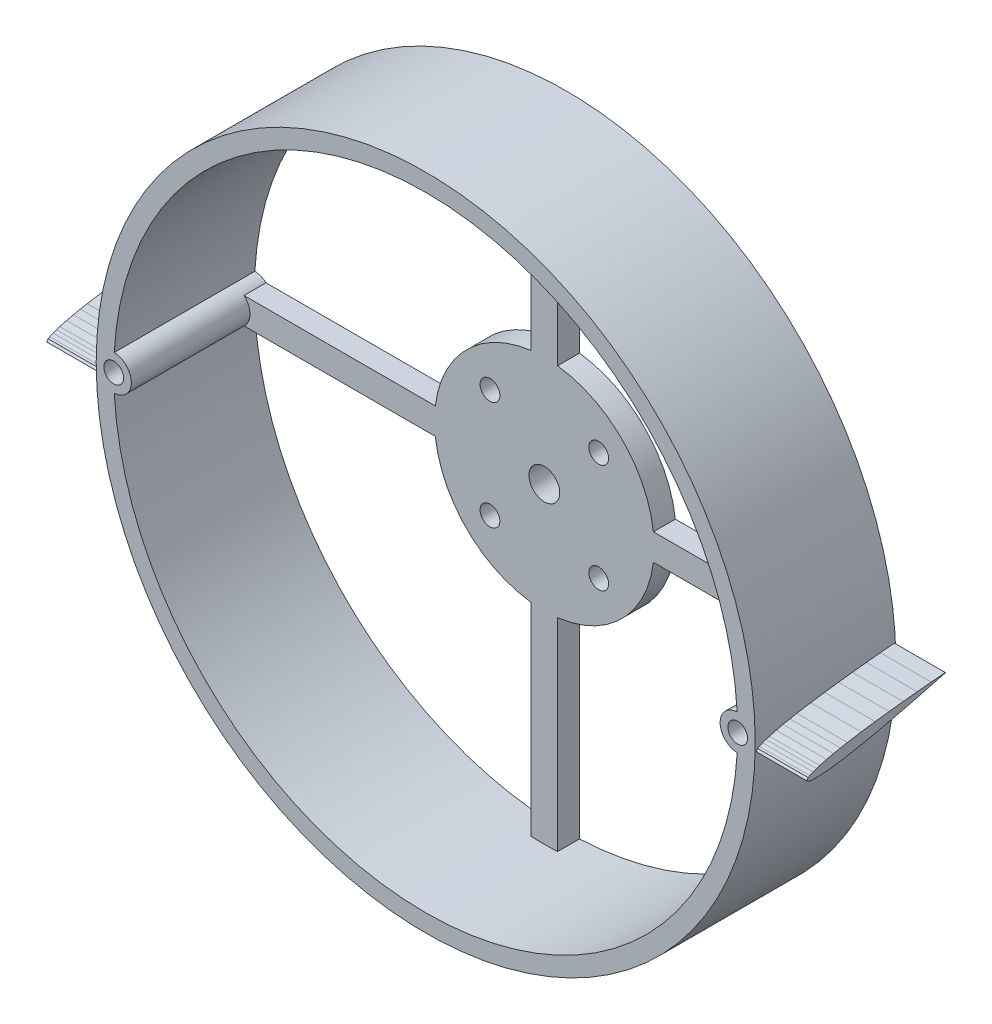
SolidWorks part; units mm, degrees
ref_plane "Front Plane" through (0, 0, 0) normal (0, 0, 1) x (1, 0, 0)
ref_plane "Top Plane" through (0, 0, 0) normal (0, 1, 0) x (1, 0, 0)
ref_plane "Right Plane" through (0, 0, 0) normal (1, 0, 0) x (0, 0, -1)
sketch "Sketch1" plane through (0, 0, 0) normal (0, 0, 1) x (1, 0, 0)
  circle A0 centre (0, 0) radius 75
  dimension "D1" = 150
extrude "Boss-Extrude1" add sketch "Sketch1" along normal blind 5
sketch "Sketch2" plane through (0, 0, 5) normal (0, 0, 1) x (1, 0, 0)
  circle A0 centre (0, 0) radius 3.5
  dimension "D1" = 7
extrude "Cut-Extrude1" cut sketch "Sketch2" against normal through all
sketch "Sketch7" plane through (0, 0, 5) normal (0, 0, 1) x (1, 0, 0)
  line L0 (-707.1068, -707.1068) -> (34648.2323, 34648.2323) construction
  line L1 (-1000, 0) -> (49000, 0) construction
  circle A0 centre (0, 0) radius 17.5 construction
  circle A1 centre (12.3744, 12.3744) radius 2.25
  dimension "D1" = 35
  dimension "D2" = 4.5
  dimension "D3" = 45
extrude "Cut-Extrude6" cut sketch "Sketch7" against normal through all
pattern_circular "CirPattern1" count 4 over 360 about axis through (0, 0, 5) along (0, 0, 1) of "Cut-Extrude6"
sketch "Sketch4" plane through (0, 0, 5) normal (0, 0, 1) x (1, 0, 0)
  line L12 (0, -1000) -> (0, 49000) construction
  line L13 (-1000, 0) -> (49000, 0) construction
  line L14 (-70.9366, -3) -> (-24.8193, -3)
  line L17 (-3, -70.9366) -> (-3, -24.8193)
  line L18 (-1000, -3) -> (49000, -3) construction
  line L20 (-3, -1000) -> (-3, 49000) construction
  arc A3 (-24.8193, -3) -> (-3, -24.8193) centre (0, 0) ccw
  arc A4 (-70.9366, -3) -> (-3, -70.9366) centre (0, 0) ccw
  circle A5 centre (0, 0) radius 75 construction
  dimension "D1" = 50
  dimension "D2" = 3
  dimension "D6" = 4
  dimension "D5" = 3
extrude "Cut-Extrude3" cut sketch "Sketch4" against normal through all
pattern_circular "CirPattern2" count 4 over 360 about axis through (0, 0, 5) along (0, 0, 1) of "Cut-Extrude3"
sketch "Sketch8" plane through (0, 0, 5) normal (0, 0, 1) x (1, 0, 0)
  circle A0 centre (0, 0) radius 75
  circle A1 centre (0, 0) radius 71
  circle A2 centre (0, 0) radius 75 construction
extrude "Boss-Extrude2" add sketch "Sketch8" along normal blind 27
sketch "Sketch9" plane through (0, 0, 0) normal (0, 0, 1) x (1, 0, 0)
  circle A0 centre (-71, 0) radius 4
  arc A1 (-70.9366, 3) -> (-70.9366, -3) centre (0, 0) ccw construction
  dimension "D1" = 8
extrude "Boss-Extrude3" add sketch "Sketch9" along normal up to surface (32 mm away) up to face at (75, 0, 32)
sketch "Sketch10" plane through (0, 0, 32) normal (0, 0, 1) x (1, 0, 0)
  circle A0 centre (-71, 0) radius 2.25
  dimension "D1" = 4.5
extrude "Cut-Extrude7" cut sketch "Sketch10" against normal through all
mirror "Mirror2" about plane through (0, 0, 0) normal (1, 0, 0) of "Cut-Extrude7", "Boss-Extrude3"
ref_axis "Axis1" through (-71, 0, 0) along (0, 0, 1)
ref_plane "Plane1" through (-74, 0, 0) normal (1, 0, 0) x (0, 0, -1)
sketch "Sketch14" plane through (-74, 0, 0) normal (1, 0, 0) x (0, 0, -1)
  line L0 (-20.8717, -2.2051) -> (-21.6499, 2.2081) construction
  line L1 (-10.3642, -0.3523) -> (-11.1424, 4.0608) construction
  line L2 (0.1433, 1.5005) -> (-0.6349, 5.9136) construction
  line L3 (-0.2513, 3.7386) -> (-1.8515, 3.5972)
  line L4 (-1.8515, 3.5972) -> (-3.4518, 3.4559)
  line L5 (-3.4518, 3.4559) -> (-6.6466, 3.1418)
  line L6 (-6.6466, 3.1418) -> (-9.8378, 2.8066)
  line L7 (-9.8378, 2.8066) -> (-13.0234, 2.4399)
  line L8 (-13.0234, 2.4399) -> (-16.2034, 2.0417)
  line L9 (-16.2034, 2.0417) -> (-19.3742, 1.5909)
  line L10 (-19.3742, 1.5909) -> (-22.5339, 1.0772)
  line L11 (-22.5339, 1.0772) -> (-24.1082, 0.7887)
  line L12 (-24.1082, 0.7887) -> (-25.6769, 0.4688)
  line L13 (-25.6769, 0.4688) -> (-27.2382, 0.1068)
  line L14 (-27.2382, 0.1068) -> (-28.7902, -0.3077)
  line L15 (-28.7902, -0.3077) -> (-29.5598, -0.5517)
  line L16 (-29.5598, -0.5517) -> (-30.3237, -0.8273)
  line L17 (-30.3237, -0.8273) -> (-31.0766, -1.1659)
  line L18 (-31.0766, -1.1659) -> (-31.4394, -1.3815)
  line L19 (-31.4394, -1.3815) -> (-31.7683, -1.8512)
  line L20 (-31.7683, -1.8512) -> (-31.2986, -2.1801)
  line L21 (-31.2986, -2.1801) -> (-30.8839, -2.2587)
  line L22 (-30.8839, -2.2587) -> (-30.0606, -2.3194)
  line L23 (-30.0606, -2.3194) -> (-29.2485, -2.317)
  line L24 (-29.2485, -2.317) -> (-28.4419, -2.2831)
  line L25 (-28.4419, -2.2831) -> (-26.8417, -2.1418)
  line L26 (-26.8417, -2.1418) -> (-25.2507, -1.948)
  line L27 (-25.2507, -1.948) -> (-23.6672, -1.7121)
  line L28 (-23.6672, -1.7121) -> (-22.0892, -1.4447)
  line L29 (-22.0892, -1.4447) -> (-18.9444, -0.8468)
  line L30 (-18.9444, -0.8468) -> (-15.8107, -0.1859)
  line L31 (-15.8107, -0.1859) -> (-12.6862, 0.5275)
  line L32 (-12.6862, 0.5275) -> (-9.5673, 1.2725)
  line L33 (-9.5673, 1.2725) -> (-6.4539, 2.049)
  line L34 (-6.4539, 2.049) -> (-3.3443, 2.8465)
  line L35 (-3.3443, 2.8465) -> (-1.7923, 3.261)
  line L36 (-1.7923, 3.261) -> (-0.2402, 3.6755)
  line L37 (-31.7683, -1.8512) -> (-0.2458, 3.707) construction
  line L38 (-32.714, -2.018) -> (0.6999, 3.8738) construction
  line L39 (-31.3792, -4.0578) -> (-32.1574, 0.3553) construction
  line L40 (-0.2233, 3.711) -> (-31.7683, -1.8512) construction
  line L41 (-1000, 1.8295) -> (49000, 1.8295) construction
  line L42 (-0.2513, 3.7386) -> (-0.2402, 3.6755)
extrude "Boss-Extrude5" add sketch "Sketch14" against normal blind 12.5
mirror "Mirror3" about plane through (0, 0, 0) normal (1, 0, 0) of "Boss-Extrude5"
